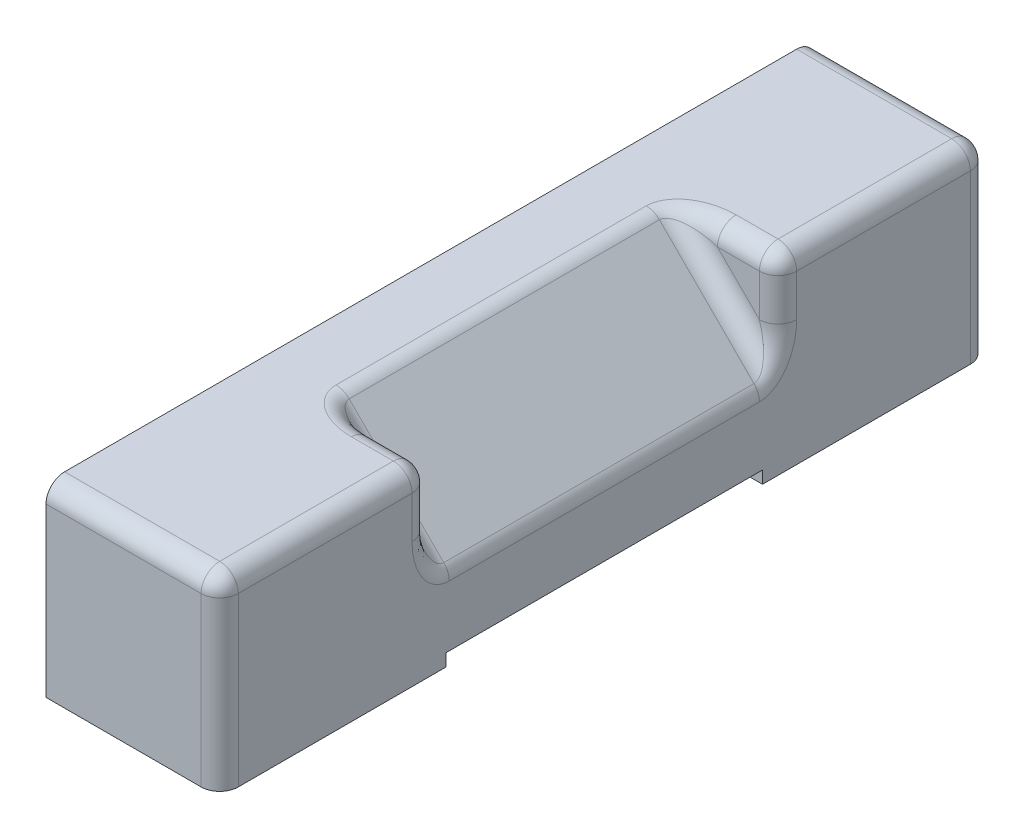
SolidWorks part; units mm, degrees
ref_plane "Front Plane" through (0, 0, 0) normal (0, 0, 1) x (1, 0, 0)
ref_plane "Top Plane" through (0, 0, 0) normal (0, 1, 0) x (1, 0, 0)
ref_plane "Right Plane" through (0, 0, 0) normal (1, 0, 0) x (0, 0, -1)
sketch "Sketch2" plane through (0, 0, 0) normal (1, 0, 0) x (0, 0, -1)
  line L1 (-62, 0) -> (62, 0)
  line L2 (-62, 0) -> (-62, 30)
  line L3 (-62, 30) -> (62, 30)
  line L4 (62, 0) -> (62, 30)
  dimension "D1" = 124
  dimension "D2" = 30
extrude "Boss-Extrude2" add sketch "Sketch2" along normal blind 28 contours L2 L1 L4 L3
sketch "Sketch3" plane through (0, 0, 0) normal (-1, 0, 0) x (0, 0, 1)
  line L4 (-60, 8.35) -> (-54, 8.35)
  line L5 (-54, 8.35) -> (-54, 11.35)
  line L6 (-54, 11.35) -> (-60, 11.35)
  line L7 (54, 11.35) -> (60, 11.35)
  line L8 (60, 28) -> (-60, 28)
  line L9 (-60, 28) -> (-60, 2)
  line L10 (-60, 2) -> (60, 2)
  line L11 (60, 2) -> (60, 28)
  line L12 (60, 28) -> (-60, 28)
  line L13 (-60, 28) -> (-60, 11.35)
  line L14 (-60, 2) -> (60, 2)
  line L15 (60, 2) -> (60, 8.35)
  line L16 (54, 11.35) -> (54, 8.35)
  line L17 (0, 28) -> (0, 2) construction
  line L18 (-54, 8.35) -> (0, 8.35) construction
  line L19 (54, 8.35) -> (60, 8.35)
  line L20 (0, 8.35) -> (54, 8.35) construction
  line L21 (-60, 11.35) -> (-60, 8.35) construction
  line L22 (-60, 8.35) -> (-60, 2)
  line L23 (60, 8.35) -> (60, 11.35) construction
  line L24 (60, 11.35) -> (60, 28)
  dimension "D2" = 6
  dimension "D3" = 3
  dimension "D4" = 6.35
  dimension "D1" = 2
extrude "Cut-Extrude1" cut sketch "Sketch3" against normal offset from surface (26 mm away) 2 up to face at (28, 15, 0)
sketch "Sketch4" plane through (0, 0, 0) normal (0, -1, 0) x (1, 0, 0)
  line L0 (28, 62) -> (28, -62) construction
  line L1 (0, 25.5) -> (28, 25.5)
  line L2 (0, 25.5) -> (0, -25.5)
  line L3 (0, -25.5) -> (28, -25.5)
  line L4 (28, 25.5) -> (28, -25.5)
  line L5 (0, 25.5) -> (28, -25.5) construction
  line L6 (0, -25.5) -> (28, 25.5) construction
  line L7 (0, 62) -> (0, -62) construction
  line L8 (0, 0) -> (28, 0) construction
  point P0 (14, 0)
  dimension "D1" = 51
extrude "Cut-Extrude2" cut sketch "Sketch4" against normal blind 2
fillet "Fillet1" radius 3 4 edges at (28, 15, 62) (28, 15, -62) (26, 19.675, 60) (26, 19.675, -60)
sketch "Sketch5" plane through (0, 0, 0) normal (0, -1, 0) x (1, 0, 0)
  line L0 (0, -54) -> (20, -54)
  line L1 (20, -54) -> (20, -25.5)
  line L2 (20, 25.5) -> (20, 54)
  line L3 (20, 54) -> (0, 54)
  line L4 (28, 25.5) -> (28, 59)
  line L5 (25, 62) -> (0, 62)
  line L6 (0, 62) -> (0, 25.5)
  line L7 (0, 25.5) -> (28, 25.5)
  line L8 (28, 25.5) -> (28, 59)
  line L9 (25, 62) -> (0, 62)
  line L10 (0, 62) -> (0, 25.5)
  line L11 (0, 25.5) -> (28, 25.5)
  line L12 (0, -62) -> (25, -62)
  line L13 (28, -59) -> (28, -25.5)
  line L14 (28, -25.5) -> (0, -25.5)
  line L15 (0, -25.5) -> (0, -62)
  line L16 (0, -62) -> (25, -62)
  line L17 (28, -59) -> (28, -25.5)
  line L18 (28, -25.5) -> (0, -25.5)
  line L19 (0, -25.5) -> (0, -62)
  arc A0 (20, -54) -> (20, -54) centre (20, -54) ccw
  arc A1 (28, 59) -> (25, 62) centre (25, 59) ccw
  arc A2 (28, 59) -> (25, 62) centre (25, 59) ccw
  arc A3 (25, -62) -> (28, -59) centre (25, -59) ccw
  arc A4 (25, -62) -> (28, -59) centre (25, -59) ccw
  arc A5 (20, 54) -> (20, 54) centre (20, 54) ccw
  line M14 (28, -25.5) -> (0, -25.5)
  line M15 (0, -25.5) -> (0, -62)
  dimension "D1" = 0
  dimension "D2" = 0
  dimension "D3" = 8
extrude "Cut-Extrude3" cut sketch "Sketch5" against normal blind 3 contours L10 L11 L2 L3 | L0 L1 M14 M15 region at (10, 0, -39.75) region at (10, 0, 39.75)
sketch "Sketch6" plane through (0, 0, 0) normal (0, 0, 1) x (1, 0, 0)
  line L0 (8.1716, 30) -> (28, 10.1716)
  line L1 (25, 30) -> (0, 30) construction
  line L2 (28, 30) -> (28, 0) construction
  line L3 (8.1716, 30) -> (28, 30)
  line L4 (28, 30) -> (28, 10.1716)
  line L5 (11, 30) -> (28, 13)
  dimension "D1" = 45
  dimension "D2" = 2
  dimension "D3" = 17
extrude "Boss-Extrude4" add sketch "Sketch6" along normal mid plane 60 contours L3 L5 L4 | L5 L3 L0 L4 region at (18.7748, 20.7748, 0) region at (22.3333, 24.3333, 0)
extrude "Cut-Extrude5" cut sketch "Sketch6<3>" against normal mid plane 56 contours L3 L5 L4 region at (22.3333, 24.3333, 0)
sketch "Sketch6<3>" plane through (0, 0, 0) normal (0, 0, 1) x (1, 0, 0) same geometry as "Sketch6"
fillet "Fillet2" radius 3 22 edges at (11, 30, 0) (28, 13, 0) (19.5, 21.5, 28) (28, 21.5, 28) (19.5, 30, 28) (19.5, 21.5, -28) (28, 21.5, -28) (19.5, 30, -28) (12.5, 30, 62) (27.1213, 30, 61.1213) (12.5, 30, -62) (27.1213, 30, -61.1213) (28, 30, 43.5) (28, 30, -43.5) (10.1716, 28, 0) (26, 12.1716, 0) (18.0858, 20.0858, -30) (26, 20.0858, -30) (18.0858, 28, -30) (18.0858, 20.0858, 30) (18.0858, 28, 30) (26, 20.0858, 30)
equation "\"cm\"=46"
